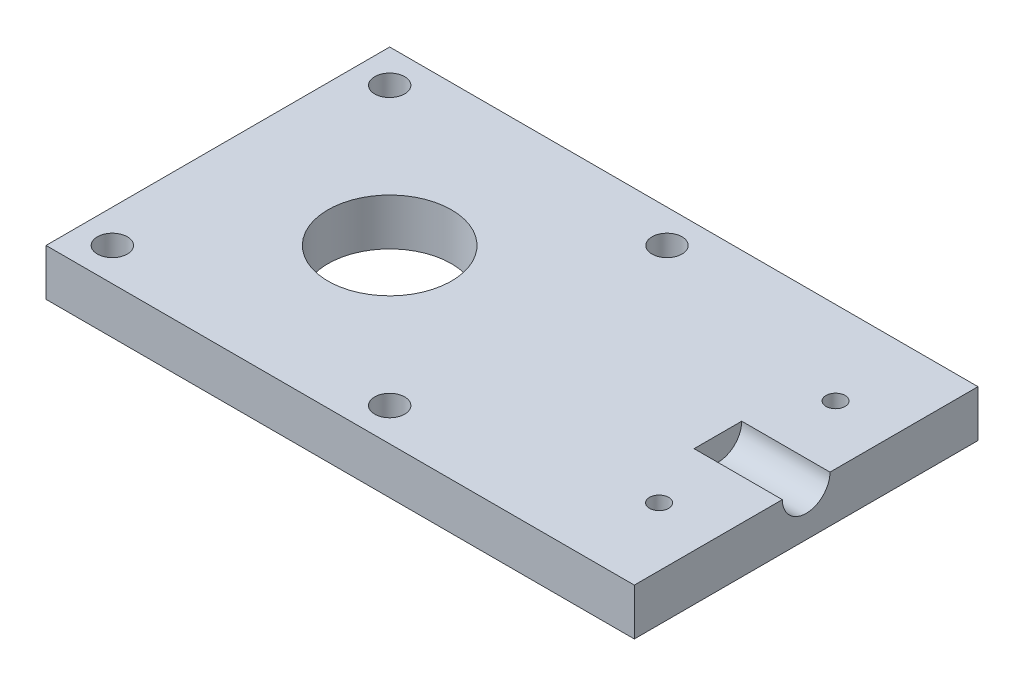
SolidWorks part; units mm, degrees
ref_plane "Top Plane" through (0, 0, 0) normal (0, 0, 1) x (1, 0, 0)
ref_plane "Front Plane" through (0, 0, 0) normal (0, 1, 0) x (1, 0, 0)
ref_plane "Right Plane" through (0, 0, 0) normal (1, 0, 0) x (0, 0, -1)
sketch "Sketch1" plane through (0, -110.0687, 0) normal (0, -1, 0) x (1, 0, 0)
  line L0 (85.5067, 86.6091) -> (85.5067, 56.6091) construction
  line L1 (-4.4933, 100.8191) -> (95.5067, 100.8191)
  line L2 (-4.4933, 100.8191) -> (-4.4933, 42.3991)
  line L3 (-4.4933, 42.3991) -> (95.5067, 42.3991)
  line L4 (95.5067, 100.8191) -> (95.5067, 42.3991)
  circle A0 centre (1.1467, 95.1791) radius 2.55
  circle A1 centre (1.1467, 48.0391) radius 2.55
  circle A2 centre (48.2867, 48.0391) radius 2.55
  circle A3 centre (48.2867, 95.1791) radius 2.55
  circle A4 centre (1.1467, 95.1791) radius 2.1 construction
  circle A5 centre (1.1467, 48.0391) radius 2.1 construction
  circle A6 centre (48.2867, 48.0391) radius 2.1 construction
  circle A7 centre (48.2867, 95.1791) radius 2.1 construction
  circle A10 centre (85.5067, 86.6091) radius 1.625
  circle A11 centre (85.5067, 56.6091) radius 1.625
  circle A14 centre (24.7167, 71.6091) radius 10.5
  circle A15 centre (24.7167, 71.6091) radius 10.5
  point P29 (-4.4933, 71.6091)
  point P30 (85.5067, 71.6091)
  dimension "D1" = 5.1
  dimension "D2" = 3.25
  dimension "D3" = 30
  dimension "D4" = 100
  dimension "D5" = 10
  dimension "D6" = 0.5
extrude "Boss-Extrude1" add sketch "Sketch1" along normal blind 7.9375
cosmetic thread "Cosmetic Thread3"
cosmetic thread "Cosmetic Thread4"
ref_plane "Plane1" through (0, -114.0374, 0) normal (0, -1, 0) x (-1, 0, 0)
extrude "Cut-Extrude1" cut sketch "Sketch2" against normal blind 15
sketch "Sketch2" plane through (95.5067, -1.5875, 13.9181) normal (1, 0, 0) x (0, 0, -1)
  circle A0 centre (-57.691, -108.4812) radius 4.05
  point P2 (-59.8912, -131.6563)
  point P3 (0, 0)
  point P6 (-40.0342, -108.4812)
  point P9 (0, 0)
